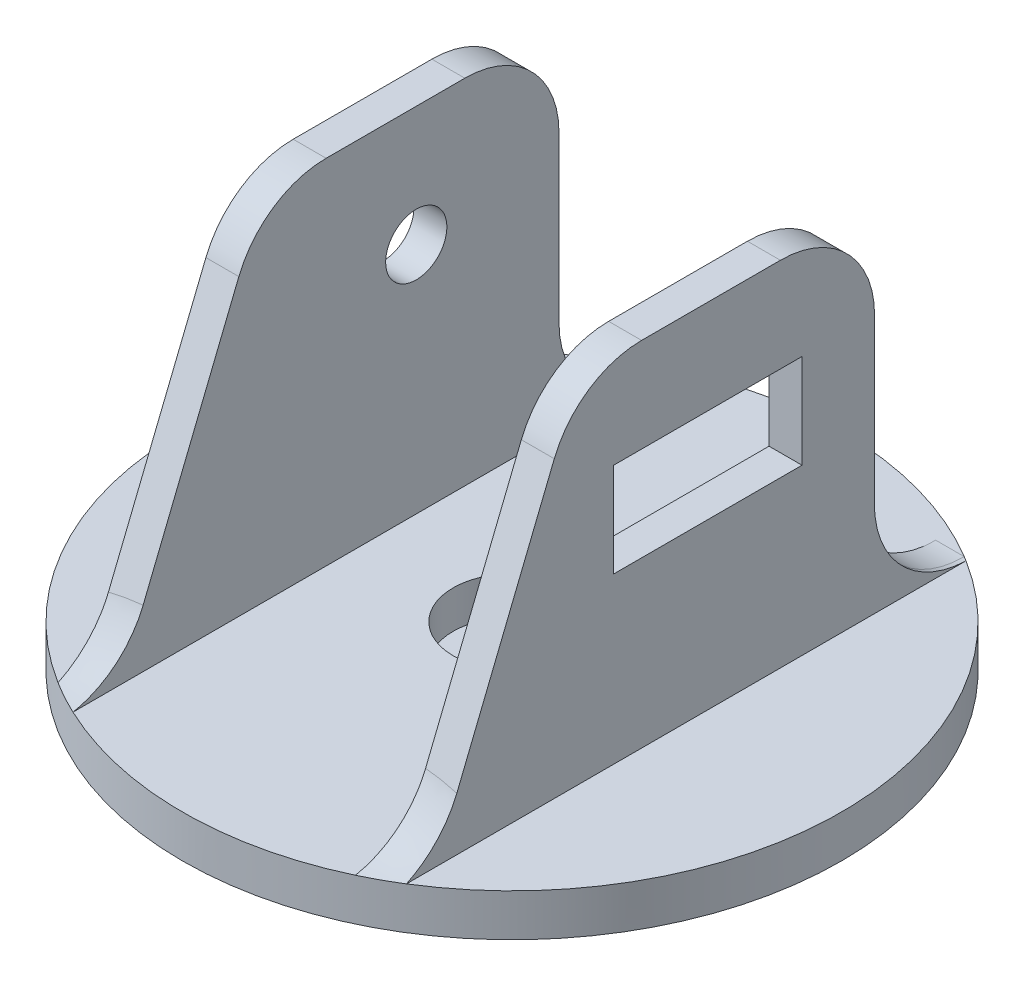
SolidWorks part; units mm, degrees
ref_plane "Front Plane" through (0, 0, 0) normal (0, 0, 1) x (1, 0, 0)
ref_plane "Top Plane" through (0, 0, 0) normal (0, 1, 0) x (1, 0, 0)
ref_plane "Right Plane" through (0, 0, 0) normal (1, 0, 0) x (0, 0, -1)
sketch "Sketch7" plane through (0, 0, 0) normal (0, 1, 0) x (1, 0, 0)
  circle A0 centre (0, 0) radius 70
  dimension "D1" = 140
extrude "Boss-Extrude3" add sketch "Sketch7" along normal blind 9
sketch "Sketch8" plane through (0, 9, 0) normal (0, 1, 0) x (1, 0, 0)
  circle A0 centre (0, 0) radius 12.5
  dimension "D1" = 25
extrude "Cut-Extrude4" cut sketch "Sketch8" against normal blind 8
sketch "Sketch9" plane through (0, 0, 0) normal (0, -1, 0) x (1, 0, 0)
  line L0 (-14.3845, 0) -> (35.4469, 0) construction
  circle A0 centre (0, 0) radius 4.5
  circle A1 centre (0, 7.25) radius 0.75
  circle A2 centre (4, 7.25) radius 0.75
  circle A3 centre (-4, 7.25) radius 0.75
  circle A4 centre (4, -7.25) radius 0.75
  circle A5 centre (0, -7.25) radius 0.75
  circle A6 centre (-4, -7.25) radius 0.75
  dimension "D1" = 9
  dimension "D2" = 1.5
  dimension "D3" = 7.25
  dimension "D4" = 4
  dimension "D5" = 4
extrude "Cut-Extrude5" cut sketch "Sketch9" against normal blind 9
ref_plane "Plane1" through (30, 0, 0) normal (1, 0, 0) x (0, 0, -1)
sketch "Sketch10" plane through (30, 0, 0) normal (1, 0, 0) x (0, 0, -1)
  line L0 (-53.2984, 9) -> (-22.9602, 84)
  line L1 (-22.9602, 84) -> (40.0037, 84)
  line L2 (40.0037, 84) -> (40.0037, 9)
  line L3 (-53.2984, 9) -> (40.0037, 9)
  line L4 (12.5, 9) -> (-12.5, 9) construction
  line L5 (70, 9) -> (-70, 9) construction
  line L6 (-15.4036, 64) -> (24.5964, 64)
  line L7 (-15.4036, 64) -> (-15.4036, 44)
  line L8 (-15.4036, 44) -> (24.5964, 44)
  line L9 (24.5964, 64) -> (24.5964, 44)
  line L10 (-15.4036, 64) -> (24.5964, 44) construction
  line L11 (-15.4036, 44) -> (24.5964, 64) construction
  point P2 (4.5964, 54)
  dimension "D1" = 40
  dimension "D2" = 20
  dimension "D3" = 75
  dimension "D4" = 45
extrude "Boss-Extrude4" add sketch "Sketch10" along normal blind 7
ref_plane "Plane2" through (-30, 0, 0) normal (1, 0, 0) x (0, 0, -1)
sketch "Sketch11" plane through (-30, 0, 0) normal (1, 0, 0) x (0, 0, -1)
  line L0 (-53.2984, 9) -> (-22.9602, 84)
  line L1 (-22.9602, 84) -> (39.982, 84)
  line L2 (39.982, 84) -> (39.982, 9)
  line L3 (-53.2984, 9) -> (39.982, 9)
extrude "Boss-Extrude5" add sketch "Sketch11" against normal blind 7
sketch "Sketch12" plane through (-37, 0, 0) normal (-1, 0, 0) x (0, 0, 1)
  line L0 (-39.982, 84) -> (22.9602, 84) construction
  line L1 (-39.982, 9) -> (-39.982, 84) construction
  circle A0 centre (-9.662, 58.56) radius 6.5
  dimension "D3" = 13
  dimension "D1" = 25.44
  dimension "D2" = 30.32
extrude "Cut-Extrude6" cut sketch "Sketch12" against normal blind 7
fillet "Fillet7" radius 20 4 edges at (33.5, 9, -40.0037) (-33.5, 9, -39.982) (-33.5, 9, 53.2984) (33.5, 9, 53.2984)
fillet "Fillet10" radius 20 4 edges at (-33.5, 84, 22.9602) (-33.5, 84, -39.982) (33.5, 84, -40.0037) (33.5, 84, 22.9602)
